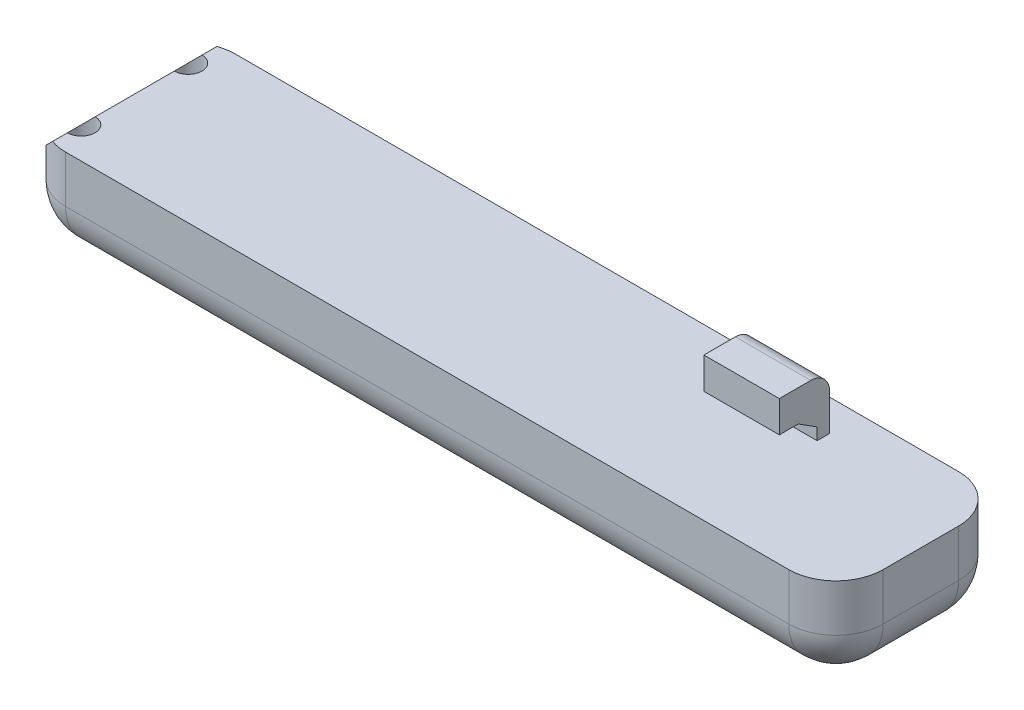
SolidWorks part; units mm, degrees
ref_plane "Front Plane" through (0, 0, 0) normal (0, 0, 1) x (1, 0, 0)
ref_plane "Top Plane" through (0, 0, 0) normal (0, 1, 0) x (1, 0, 0)
ref_plane "Right Plane" through (0, 0, 0) normal (1, 0, 0) x (0, 0, -1)
sketch "Sketch1" plane through (0, 0, 0) normal (0, 1, 0) x (1, 0, 0)
  line L1 (7.5, 27) -> (122.5, 27)
  line L2 (0, 19.5) -> (0, 7.5)
  line L3 (7.5, 0) -> (122.5, 0)
  line L4 (130, 19.5) -> (130, 7.5)
  arc A0 (130, 19.5) -> (122.5, 27) centre (122.5, 19.5) ccw
  arc A1 (130, 7.5) -> (122.5, 0) centre (122.5, 7.5) cw
  arc A2 (7.5, 0) -> (0, 7.5) centre (7.5, 7.5) cw
  arc A3 (0, 19.5) -> (7.5, 27) centre (7.5, 19.5) cw
  point P12 (0, 0)
  point P15 (0, 27)
  dimension "D3" = 7.5
  dimension "D1" = 130
  dimension "D2" = 27
extrude "Boss-Extrude1" add sketch "Sketch1" along normal blind 15
fillet "Fillet1" radius 7.5 1 edges at (65, 0, 0) type face fillet first side face at (65, 0, -13.5) second side face at (65, 7.5, 0)
sketch "Sketch2" plane through (0, 15, 0) normal (0, 1, 0) x (1, 0, 0)
  line L0 (0, 19.5) -> (0, 7.5) construction
  line L1 (122.5, 27) -> (7.5, 27) construction
  line L2 (7.5, 0) -> (122.5, 0) construction
  circle A0 centre (5, 22) radius 2.2
  circle A1 centre (5, 5) radius 2.2
  dimension "D1" = 4.4
  dimension "D2" = 4.4
  dimension "D3" = 5
  dimension "D4" = 5
  dimension "D5" = 5
  dimension "D6" = 5
chamfer "Chamfer1" distance 5 angle 45 1 edges at (0, 15, -13.5) tangent propagation no
extrude "Cut-Extrude1" cut sketch "Sketch2" against normal blind 10
sketch "Sketch3" plane through (0, 15, 0) normal (0, 1, 0) x (1, 0, 0)
  line L0 (5, 26.5711) -> (5, 24.2) construction
  line L1 (95, 22) -> (107, 22)
  line L2 (95, 22) -> (95, 20)
  line L3 (95, 20) -> (107, 20)
  line L4 (107, 22) -> (107, 20)
  line L7 (7.5, 0) -> (122.5, 0) construction
  point P6 (101, 20)
  dimension "D1" = 90
  dimension "D2" = 12
  dimension "D3" = 2
  dimension "D5" = 20
extrude "Boss-Extrude2" add sketch "Sketch3" along normal blind 3.8
sketch "Sketch4" plane through (0, 18.8, 0) normal (0, 1, 0) x (1, 0, 0)
  line L0 (107, 20) -> (107, 22) construction
  line L1 (95, 22) -> (107, 22)
  line L2 (95, 22) -> (95, 14)
  line L3 (95, 14) -> (107, 14)
  line L4 (107, 22) -> (107, 14)
  line L5 (95, 22) -> (95, 20) construction
  line L13 (107, 22) -> (95, 22) construction
  dimension "D1" = 8
extrude "Boss-Extrude3" add sketch "Sketch4" along normal blind 5
fillet "Fillet2" radius 3 1 edges at (101, 23.8, -22) type face fillet first side face at (101, 23.8, -18) second side face at (101, 19.4, -22)
sketch "Sketch5" plane through (95, 0, 0) normal (-1, 0, 0) x (0, 0, 1)
  line L0 (-20, 18.8) -> (-17, 18.8)
  line L1 (-20, 18.8) -> (-14, 18.8) construction
  line L4 (-20, 18.8) -> (-20, 16.9)
  line L6 (-20, 18.8) -> (-20, 15) construction
  line L7 (-20, 16.9) -> (-17, 18.8)
extrude "Boss-Extrude4" add sketch "Sketch5" against normal blind 12
